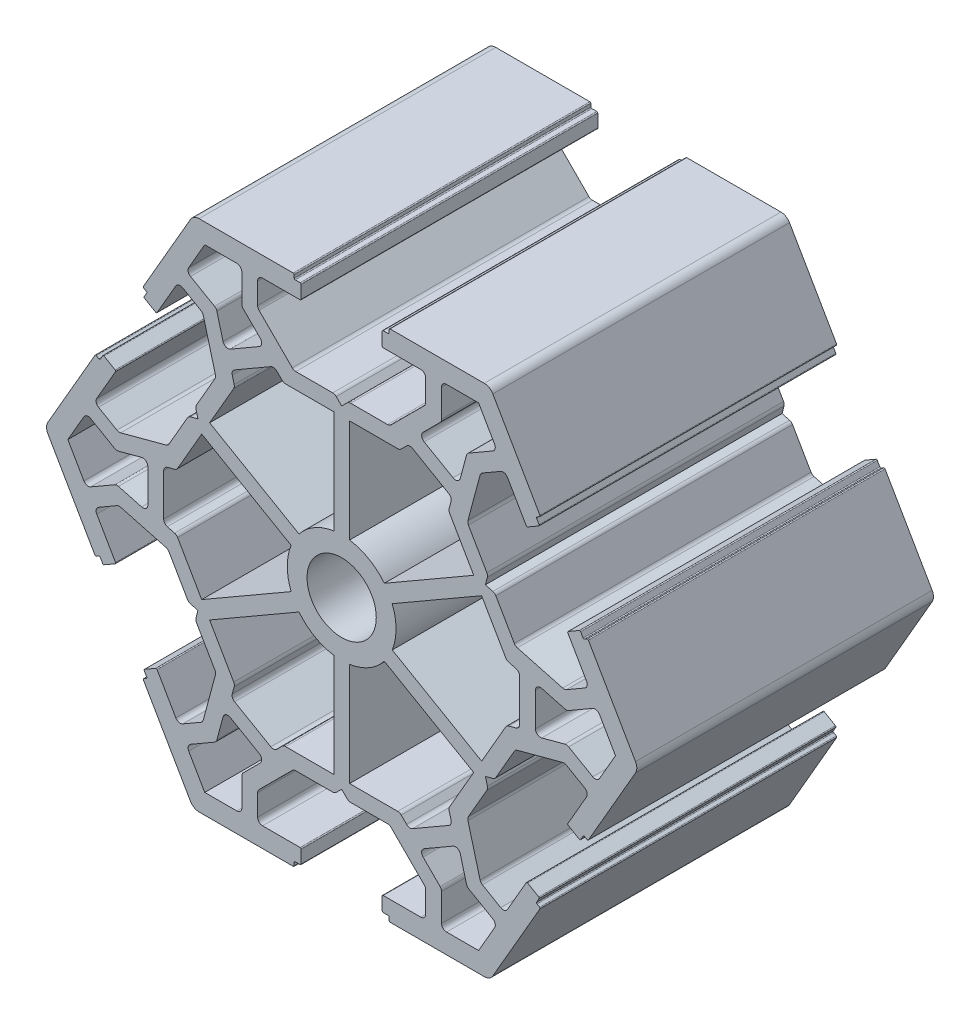
SolidWorks part; units mm, degrees
material "6061 Alaşım"
ref_plane "Ön Düzlem" through (0, 0, 0) normal (0, 0, 1) x (1, 0, 0)
ref_plane "Üst Düzlem" through (0, 0, 0) normal (0, 1, 0) x (1, 0, 0)
ref_plane "Sağ Düzlem" through (0, 0, 0) normal (1, 0, 0) x (0, 0, -1)
sketch "Çizim1" plane through (0, 0, 0) normal (0, 0, 1) x (1, 0, 0)
  line L0 (0, 0) -> (-15, 25.9808) construction
  line L1 (-30, 0) -> (-15, -25.9808) construction
  line L2 (-15, -25.9808) -> (15, -25.9808) construction
  line L3 (15, -25.9808) -> (30, 0) construction
  line L4 (30, 0) -> (15, 25.9808) construction
  line L5 (15, 25.9808) -> (-15, 25.9808) construction
  line L6 (-15, 25.9808) -> (-30, 0) construction
  line L7 (0, 0) -> (-30, 0) construction
  line L8 (0, 0) -> (15, 25.9808) construction
  line L9 (-15.2887, 25.4808) -> (-20.05, 17.2339)
  line L10 (-20.0134, 17.0973) -> (-19.7536, 16.9473)
  line L11 (-19.717, 16.8107) -> (-19.967, 16.3777)
  line L12 (-19.9304, 16.2411) -> (-18.8046, 15.5911)
  line L13 (-18.6679, 15.6277) -> (-16.7679, 18.9186)
  line L14 (-22.5, 12.9904) -> (0, 0) construction
  line L15 (-16.0849, 19.1016) -> (-14.2291, 18.0302)
  line L16 (-13.9962, 17.7265) -> (-12.7674, 13.1407)
  line L17 (-12.8173, 12.7612) -> (-14.6852, 9.526)
  line L18 (-14.7352, 9.1465) -> (-14.5326, 8.3904)
  line L19 (-13.3531, 8.6332) -> (-10.9181, 12.8509)
  line L20 (-10.8681, 13.2303) -> (-11.0658, 13.9679)
  line L21 (-10.8328, 14.5303) -> (-7.1672, 16.6466)
  line L22 (-13.3531, 8.6332) -> (-4.3125, 3.4136)
  line L23 (-13.8453, 23.9808) -> (-15.4679, 21.1703)
  line L24 (-15.2849, 20.4872) -> (-12.8552, 19.0844)
  line L25 (-12.6222, 18.7808) -> (-11.9935, 16.4345)
  line L26 (-11.2606, 16.1308) -> (-8.3394, 17.8173)
  line L27 (-14.5326, 8.3904) -> (-4.7631, 2.75) construction
  line L29 (-9.8, 16.9741) -> (-9, 15.5885)
  line L30 (-9.9536, 20.3216) -> (-8.2359, 18.6039)
  line L31 (-10.1, 23.4808) -> (-10.1, 20.6751)
  line L32 (-13.8453, 23.9808) -> (-10.6, 23.9808)
  line L33 (-14.4226, 25.9808) -> (-4.9, 25.9808)
  line L34 (-4.8, 25.8808) -> (-4.8, 25.5808)
  line L35 (-4.7, 25.4808) -> (-4.2, 25.4808)
  line L36 (-4.1, 25.3808) -> (-4.1, 24.0808)
  line L37 (-4.2, 23.9808) -> (-8, 23.9808)
  line L38 (-8.5, 23.4808) -> (-8.5, 21.3379)
  line L39 (-8.3536, 20.9843) -> (-4.9964, 17.6272)
  line L40 (-4.6429, 17.4808) -> (-0.9071, 17.4808)
  line L41 (-0.5536, 17.3343) -> (0, 16.7808)
  line L42 (0, 16.7808) -> (0, 5.5) construction
  line L43 (-0.8, 15.8808) -> (-0.8, 5.4415)
  line L44 (-0.8, 15.8808) -> (-5.6701, 15.8808)
  line L45 (-6.0237, 16.0272) -> (-6.5636, 16.5672)
  line L46 (15.2887, 25.4808) -> (20.05, 17.2339)
  line L47 (20.0134, 17.0973) -> (19.7536, 16.9473)
  line L48 (19.717, 16.8107) -> (19.967, 16.3777)
  line L49 (19.9304, 16.2411) -> (18.8046, 15.5911)
  line L50 (18.6679, 15.6277) -> (16.7679, 18.9186)
  line L51 (16.0849, 19.1016) -> (14.2291, 18.0302)
  line L52 (13.9962, 17.7265) -> (12.7674, 13.1407)
  line L53 (12.8173, 12.7612) -> (14.6852, 9.526)
  line L54 (14.7352, 9.1465) -> (14.5326, 8.3904)
  line L55 (14.5326, 8.3904) -> (4.7631, 2.75) construction
  line L56 (13.3531, 8.6332) -> (4.3125, 3.4136)
  line L57 (13.3531, 8.6332) -> (10.9181, 12.8509)
  line L58 (10.8681, 13.2303) -> (11.0658, 13.9679)
  line L59 (7.1672, 16.6466) -> (10.8328, 14.5303)
  line L60 (6.0237, 16.0272) -> (6.5636, 16.5672)
  line L61 (0.8, 15.8808) -> (5.6701, 15.8808)
  line L62 (0.8, 15.8808) -> (0.8, 5.4415)
  line L63 (0, 16.7808) -> (0, 5.5) construction
  line L64 (0.5536, 17.3343) -> (0, 16.7808)
  line L65 (4.6429, 17.4808) -> (0.9071, 17.4808)
  line L66 (8.3536, 20.9843) -> (4.9964, 17.6272)
  line L67 (8.5, 23.4808) -> (8.5, 21.3379)
  line L68 (4.2, 23.9808) -> (8, 23.9808)
  line L69 (4.1, 25.3808) -> (4.1, 24.0808)
  line L70 (4.7, 25.4808) -> (4.2, 25.4808)
  line L71 (4.8, 25.8808) -> (4.8, 25.5808)
  line L72 (14.4226, 25.9808) -> (4.9, 25.9808)
  line L73 (13.8453, 23.9808) -> (15.4679, 21.1703)
  line L74 (15.2849, 20.4872) -> (12.8552, 19.0844)
  line L75 (12.6222, 18.7808) -> (11.9935, 16.4345)
  line L76 (8.3394, 17.8173) -> (11.2606, 16.1308)
  line L77 (9.9536, 20.3216) -> (8.2359, 18.6039)
  line L78 (10.1, 23.4808) -> (10.1, 20.6751)
  line L79 (13.8453, 23.9808) -> (10.6, 23.9808)
  line L80 (29.7113, -0.5) -> (24.95, -8.7469)
  line L81 (24.8134, -8.7835) -> (24.5536, -8.6335)
  line L82 (24.417, -8.6701) -> (24.167, -9.1031)
  line L83 (24.0304, -9.1397) -> (22.9046, -8.4897)
  line L84 (22.8679, -8.3531) -> (24.7679, -5.0622)
  line L85 (24.5849, -4.3792) -> (22.7291, -3.3077)
  line L86 (22.3497, -3.2578) -> (17.7638, -4.4866)
  line L87 (17.4602, -4.7195) -> (15.5923, -7.9548)
  line L88 (15.2887, -8.1878) -> (14.5326, -8.3904)
  line L89 (14.5326, -8.3904) -> (4.7631, -2.75) construction
  line L90 (14.1531, -7.2476) -> (5.1125, -2.0279)
  line L91 (14.1531, -7.2476) -> (16.5882, -3.0299)
  line L92 (16.8918, -2.7969) -> (17.6294, -2.5993)
  line L93 (18, 2.1163) -> (18, -2.1163)
  line L94 (16.8918, 2.7969) -> (17.6294, 2.5993)
  line L95 (14.1531, 7.2476) -> (16.5882, 3.0299)
  line L96 (14.1531, 7.2476) -> (5.1125, 2.0279)
  line L97 (14.5326, 8.3904) -> (4.7631, 2.75) construction
  line L98 (15.2887, 8.1878) -> (14.5326, 8.3904)
  line L99 (17.4602, 4.7195) -> (15.5923, 7.9548)
  line L100 (22.3497, 3.2578) -> (17.7638, 4.4866)
  line L101 (24.5849, 4.3792) -> (22.7291, 3.3077)
  line L102 (22.8679, 8.3531) -> (24.7679, 5.0622)
  line L103 (24.0304, 9.1397) -> (22.9046, 8.4897)
  line L104 (24.417, 8.6701) -> (24.167, 9.1031)
  line L105 (24.8134, 8.7835) -> (24.5536, 8.6335)
  line L106 (29.7113, 0.5) -> (24.95, 8.7469)
  line L107 (27.6906, 0) -> (26.0679, -2.8105)
  line L108 (25.3849, -2.9935) -> (22.9552, -1.5907)
  line L109 (22.5758, -1.5408) -> (20.2294, -2.1695)
  line L110 (19.6, 1.6865) -> (19.6, -1.6865)
  line L111 (22.5758, 1.5408) -> (20.2294, 2.1695)
  line L112 (25.3849, 2.9935) -> (22.9552, 1.5907)
  line L113 (27.6906, 0) -> (26.0679, 2.8105)
  line L114 (14.4226, -25.9808) -> (4.9, -25.9808)
  line L115 (4.8, -25.8808) -> (4.8, -25.5808)
  line L116 (4.7, -25.4808) -> (4.2, -25.4808)
  line L117 (4.1, -25.3808) -> (4.1, -24.0808)
  line L118 (4.2, -23.9808) -> (8, -23.9808)
  line L119 (8.5, -23.4808) -> (8.5, -21.3379)
  line L120 (8.3536, -20.9843) -> (4.9964, -17.6272)
  line L121 (4.6429, -17.4808) -> (0.9071, -17.4808)
  line L122 (0.5536, -17.3343) -> (0, -16.7808)
  line L123 (0, -16.7808) -> (0, -5.5) construction
  line L124 (0.8, -15.8808) -> (0.8, -5.4415)
  line L125 (0.8, -15.8808) -> (5.6701, -15.8808)
  line L126 (6.0237, -16.0272) -> (6.5636, -16.5672)
  line L127 (10.8328, -14.5303) -> (7.1672, -16.6466)
  line L128 (10.8681, -13.2303) -> (11.0658, -13.9679)
  line L129 (13.3531, -8.6332) -> (10.9181, -12.8509)
  line L130 (13.3531, -8.6332) -> (4.3125, -3.4136)
  line L131 (14.5326, -8.3904) -> (4.7631, -2.75) construction
  line L132 (14.7352, -9.1465) -> (14.5326, -8.3904)
  line L133 (12.8173, -12.7612) -> (14.6852, -9.526)
  line L134 (13.9962, -17.7265) -> (12.7674, -13.1407)
  line L135 (16.0849, -19.1016) -> (14.2291, -18.0302)
  line L136 (18.6679, -15.6277) -> (16.7679, -18.9186)
  line L137 (19.9304, -16.2411) -> (18.8046, -15.5911)
  line L138 (19.717, -16.8107) -> (19.967, -16.3777)
  line L139 (20.0134, -17.0973) -> (19.7536, -16.9473)
  line L140 (15.2887, -25.4808) -> (20.05, -17.2339)
  line L141 (13.8453, -23.9808) -> (10.6, -23.9808)
  line L142 (10.1, -23.4808) -> (10.1, -20.6751)
  line L143 (9.9536, -20.3216) -> (8.2359, -18.6039)
  line L144 (11.2606, -16.1308) -> (8.3394, -17.8173)
  line L145 (12.6222, -18.7808) -> (11.9935, -16.4345)
  line L146 (15.2849, -20.4872) -> (12.8552, -19.0844)
  line L147 (13.8453, -23.9808) -> (15.4679, -21.1703)
  line L148 (-15.2887, -25.4808) -> (-20.05, -17.2339)
  line L149 (-20.0134, -17.0973) -> (-19.7536, -16.9473)
  line L150 (-19.717, -16.8107) -> (-19.967, -16.3777)
  line L151 (-19.9304, -16.2411) -> (-18.8046, -15.5911)
  line L152 (-18.6679, -15.6277) -> (-16.7679, -18.9186)
  line L153 (-16.0849, -19.1016) -> (-14.2291, -18.0302)
  line L154 (-13.9962, -17.7265) -> (-12.7674, -13.1407)
  line L155 (-12.8173, -12.7612) -> (-14.6852, -9.526)
  line L156 (-14.7352, -9.1465) -> (-14.5326, -8.3904)
  line L157 (-14.5326, -8.3904) -> (-4.7631, -2.75) construction
  line L158 (-13.3531, -8.6332) -> (-4.3125, -3.4136)
  line L159 (-13.3531, -8.6332) -> (-10.9181, -12.8509)
  line L160 (-10.8681, -13.2303) -> (-11.0658, -13.9679)
  line L161 (-7.1672, -16.6466) -> (-10.8328, -14.5303)
  line L162 (-6.0237, -16.0272) -> (-6.5636, -16.5672)
  line L163 (-0.8, -15.8808) -> (-5.6701, -15.8808)
  line L164 (-0.8, -15.8808) -> (-0.8, -5.4415)
  line L165 (0, -16.7808) -> (0, -5.5) construction
  line L166 (-0.5536, -17.3343) -> (0, -16.7808)
  line L167 (-4.6429, -17.4808) -> (-0.9071, -17.4808)
  line L168 (-8.3536, -20.9843) -> (-4.9964, -17.6272)
  line L169 (-8.5, -23.4808) -> (-8.5, -21.3379)
  line L170 (-4.2, -23.9808) -> (-8, -23.9808)
  line L171 (-4.1, -25.3808) -> (-4.1, -24.0808)
  line L172 (-4.7, -25.4808) -> (-4.2, -25.4808)
  line L173 (-4.8, -25.8808) -> (-4.8, -25.5808)
  line L174 (-14.4226, -25.9808) -> (-4.9, -25.9808)
  line L175 (-13.8453, -23.9808) -> (-15.4679, -21.1703)
  line L176 (-15.2849, -20.4872) -> (-12.8552, -19.0844)
  line L177 (-12.6222, -18.7808) -> (-11.9935, -16.4345)
  line L178 (-8.3394, -17.8173) -> (-11.2606, -16.1308)
  line L179 (-9.9536, -20.3216) -> (-8.2359, -18.6039)
  line L180 (-10.1, -23.4808) -> (-10.1, -20.6751)
  line L181 (-13.8453, -23.9808) -> (-10.6, -23.9808)
  line L182 (-29.7113, 0.5) -> (-24.95, 8.7469)
  line L183 (-24.8134, 8.7835) -> (-24.5536, 8.6335)
  line L184 (-24.417, 8.6701) -> (-24.167, 9.1031)
  line L185 (-24.0304, 9.1397) -> (-22.9046, 8.4897)
  line L186 (-22.8679, 8.3531) -> (-24.7679, 5.0622)
  line L187 (-24.5849, 4.3792) -> (-22.7291, 3.3077)
  line L188 (-22.3497, 3.2578) -> (-17.7638, 4.4866)
  line L189 (-17.4602, 4.7195) -> (-15.5923, 7.9548)
  line L190 (-15.2887, 8.1878) -> (-14.5326, 8.3904)
  line L191 (-14.5326, 8.3904) -> (-4.7631, 2.75) construction
  line L192 (-14.1531, 7.2476) -> (-5.1125, 2.0279)
  line L193 (-14.1531, 7.2476) -> (-16.5882, 3.0299)
  line L194 (-16.8918, 2.7969) -> (-17.6294, 2.5993)
  line L195 (-18, -2.1163) -> (-18, 2.1163)
  line L196 (-16.8918, -2.7969) -> (-17.6294, -2.5993)
  line L197 (-14.1531, -7.2476) -> (-16.5882, -3.0299)
  line L198 (-14.1531, -7.2476) -> (-5.1125, -2.0279)
  line L199 (-14.5326, -8.3904) -> (-4.7631, -2.75) construction
  line L200 (-15.2887, -8.1878) -> (-14.5326, -8.3904)
  line L201 (-17.4602, -4.7195) -> (-15.5923, -7.9548)
  line L202 (-22.3497, -3.2578) -> (-17.7638, -4.4866)
  line L203 (-24.5849, -4.3792) -> (-22.7291, -3.3077)
  line L204 (-22.8679, -8.3531) -> (-24.7679, -5.0622)
  line L205 (-24.0304, -9.1397) -> (-22.9046, -8.4897)
  line L206 (-24.417, -8.6701) -> (-24.167, -9.1031)
  line L207 (-24.8134, -8.7835) -> (-24.5536, -8.6335)
  line L208 (-29.7113, -0.5) -> (-24.95, -8.7469)
  line L209 (-27.6906, 0) -> (-26.0679, 2.8105)
  line L210 (-25.3849, 2.9935) -> (-22.9552, 1.5907)
  line L211 (-22.5758, 1.5408) -> (-20.2294, 2.1695)
  line L212 (-19.6, -1.6865) -> (-19.6, 1.6865)
  line L213 (-22.5758, -1.5408) -> (-20.2294, -2.1695)
  line L214 (-25.3849, -2.9935) -> (-22.9552, -1.5907)
  line L215 (-27.6906, 0) -> (-26.0679, -2.8105)
  circle A0 centre (0, 0) radius 25.9808 construction
  circle A1 centre (0, 0) radius 5.5 construction
  arc A2 (-20.05, 17.2339) -> (-20.0134, 17.0973) centre (-19.9634, 17.1839) ccw
  arc A3 (-19.7536, 16.9473) -> (-19.717, 16.8107) centre (-19.8036, 16.8607) cw
  arc A4 (-19.967, 16.3777) -> (-19.9304, 16.2411) centre (-19.8804, 16.3277) ccw
  arc A5 (-18.8046, 15.5911) -> (-18.6679, 15.6277) centre (-18.7546, 15.6777) ccw
  arc A6 (-15.4679, 21.1703) -> (-15.2849, 20.4872) centre (-15.0349, 20.9203) ccw
  arc A7 (-16.7679, 18.9186) -> (-16.0849, 19.1016) centre (-16.3349, 18.6686) cw
  arc A8 (-14.2291, 18.0302) -> (-13.9962, 17.7265) centre (-14.4791, 17.5971) cw
  arc A9 (-12.8552, 19.0844) -> (-12.6222, 18.7808) centre (-13.1052, 18.6514) cw
  arc A10 (-11.9935, 16.4345) -> (-11.2606, 16.1308) centre (-11.5106, 16.5639) ccw
  arc A11 (-11.0658, 13.9679) -> (-10.8328, 14.5303) centre (-10.5828, 14.0973) cw
  arc A12 (-14.6852, 9.526) -> (-14.7352, 9.1465) centre (-14.2522, 9.276) ccw
  arc A13 (-12.7674, 13.1407) -> (-12.8173, 12.7612) centre (-13.2504, 13.0112) cw
  arc A14 (-10.9181, 12.8509) -> (-10.8681, 13.2303) centre (-11.3511, 13.1009) ccw
  arc A15 (-4.7631, 2.75) -> (-4.3125, 3.4136) centre (0, 0) cw
  arc A16 (-8.2359, 18.6039) -> (-8.3394, 17.8173) centre (-8.5894, 18.2504) cw
  arc A17 (-10.1, 20.6751) -> (-9.9536, 20.3216) centre (-9.6, 20.6751) ccw
  arc A18 (-10.6, 23.9808) -> (-10.1, 23.4808) centre (-10.6, 23.4808) cw
  arc A19 (-4.9, 25.9808) -> (-4.8, 25.8808) centre (-4.9, 25.8808) cw
  arc A20 (-4.8, 25.5808) -> (-4.7, 25.4808) centre (-4.7, 25.5808) ccw
  arc A21 (-4.2, 25.4808) -> (-4.1, 25.3808) centre (-4.2, 25.3808) cw
  arc A22 (-4.1, 24.0808) -> (-4.2, 23.9808) centre (-4.2, 24.0808) cw
  arc A23 (-8, 23.9808) -> (-8.5, 23.4808) centre (-8, 23.4808) ccw
  arc A24 (-8.5, 21.3379) -> (-8.3536, 20.9843) centre (-8, 21.3379) ccw
  arc A25 (-4.9964, 17.6272) -> (-4.6429, 17.4808) centre (-4.6429, 17.9808) ccw
  arc A26 (-0.9071, 17.4808) -> (-0.5536, 17.3343) centre (-0.9071, 16.9808) cw
  arc A27 (0, 5.5) -> (-0.8, 5.4415) centre (0, 0) ccw
  arc A28 (-5.6701, 15.8808) -> (-6.0237, 16.0272) centre (-5.6701, 16.3808) cw
  arc A29 (-6.5636, 16.5672) -> (-7.1672, 16.6466) centre (-6.9172, 16.2136) ccw
  arc A30 (-14.4226, 25.9808) -> (-15.2887, 25.4808) centre (-14.4226, 24.9808) ccw
  arc A31 (15.2887, 25.4808) -> (14.4226, 25.9808) centre (14.4226, 24.9808) ccw
  arc A32 (20.05, 17.2339) -> (20.0134, 17.0973) centre (19.9634, 17.1839) cw
  arc A33 (19.7536, 16.9473) -> (19.717, 16.8107) centre (19.8036, 16.8607) ccw
  arc A34 (19.967, 16.3777) -> (19.9304, 16.2411) centre (19.8804, 16.3277) cw
  arc A35 (18.8046, 15.5911) -> (18.6679, 15.6277) centre (18.7546, 15.6777) cw
  arc A36 (16.7679, 18.9186) -> (16.0849, 19.1016) centre (16.3349, 18.6686) ccw
  arc A37 (14.2291, 18.0302) -> (13.9962, 17.7265) centre (14.4791, 17.5971) ccw
  arc A38 (12.7674, 13.1407) -> (12.8173, 12.7612) centre (13.2504, 13.0112) ccw
  arc A39 (14.6852, 9.526) -> (14.7352, 9.1465) centre (14.2522, 9.276) cw
  arc A40 (4.7631, 2.75) -> (4.3125, 3.4136) centre (0, 0) ccw
  arc A41 (10.9181, 12.8509) -> (10.8681, 13.2303) centre (11.3511, 13.1009) cw
  arc A42 (11.0658, 13.9679) -> (10.8328, 14.5303) centre (10.5828, 14.0973) ccw
  arc A43 (6.5636, 16.5672) -> (7.1672, 16.6466) centre (6.9172, 16.2136) cw
  arc A44 (5.6701, 15.8808) -> (6.0237, 16.0272) centre (5.6701, 16.3808) ccw
  arc A45 (0, 5.5) -> (0.8, 5.4415) centre (0, 0) cw
  arc A46 (0.9071, 17.4808) -> (0.5536, 17.3343) centre (0.9071, 16.9808) ccw
  arc A47 (4.9964, 17.6272) -> (4.6429, 17.4808) centre (4.6429, 17.9808) cw
  arc A48 (8.5, 21.3379) -> (8.3536, 20.9843) centre (8, 21.3379) cw
  arc A49 (8, 23.9808) -> (8.5, 23.4808) centre (8, 23.4808) cw
  arc A50 (4.1, 24.0808) -> (4.2, 23.9808) centre (4.2, 24.0808) ccw
  arc A51 (4.2, 25.4808) -> (4.1, 25.3808) centre (4.2, 25.3808) ccw
  arc A52 (4.8, 25.5808) -> (4.7, 25.4808) centre (4.7, 25.5808) cw
  arc A53 (4.9, 25.9808) -> (4.8, 25.8808) centre (4.9, 25.8808) ccw
  arc A54 (15.4679, 21.1703) -> (15.2849, 20.4872) centre (15.0349, 20.9203) cw
  arc A55 (12.8552, 19.0844) -> (12.6222, 18.7808) centre (13.1052, 18.6514) ccw
  arc A56 (11.9935, 16.4345) -> (11.2606, 16.1308) centre (11.5106, 16.5639) cw
  arc A57 (8.2359, 18.6039) -> (8.3394, 17.8173) centre (8.5894, 18.2504) ccw
  arc A58 (10.1, 20.6751) -> (9.9536, 20.3216) centre (9.6, 20.6751) cw
  arc A59 (10.6, 23.9808) -> (10.1, 23.4808) centre (10.6, 23.4808) ccw
  arc A60 (29.7113, -0.5) -> (29.7113, 0.5) centre (28.8453, 0) ccw
  arc A61 (24.95, -8.7469) -> (24.8134, -8.7835) centre (24.8634, -8.6969) cw
  arc A62 (24.5536, -8.6335) -> (24.417, -8.6701) centre (24.5036, -8.7201) ccw
  arc A63 (24.167, -9.1031) -> (24.0304, -9.1397) centre (24.0804, -9.0531) cw
  arc A64 (22.9046, -8.4897) -> (22.8679, -8.3531) centre (22.9546, -8.4031) cw
  arc A65 (24.7679, -5.0622) -> (24.5849, -4.3792) centre (24.3349, -4.8122) ccw
  arc A66 (22.7291, -3.3077) -> (22.3497, -3.2578) centre (22.4791, -3.7407) ccw
  arc A67 (17.7638, -4.4866) -> (17.4602, -4.7195) centre (17.8932, -4.9695) ccw
  arc A68 (15.5923, -7.9548) -> (15.2887, -8.1878) centre (15.1593, -7.7048) cw
  arc A69 (4.7631, -2.75) -> (5.1125, -2.0279) centre (0, 0) ccw
  arc A70 (16.5882, -3.0299) -> (16.8918, -2.7969) centre (17.0212, -3.2799) cw
  arc A71 (17.6294, -2.5993) -> (18, -2.1163) centre (17.5, -2.1163) ccw
  arc A72 (17.6294, 2.5993) -> (18, 2.1163) centre (17.5, 2.1163) cw
  arc A73 (16.5882, 3.0299) -> (16.8918, 2.7969) centre (17.0212, 3.2799) ccw
  arc A74 (4.7631, 2.75) -> (5.1125, 2.0279) centre (0, 0) cw
  arc A75 (15.5923, 7.9548) -> (15.2887, 8.1878) centre (15.1593, 7.7048) ccw
  arc A76 (17.7638, 4.4866) -> (17.4602, 4.7195) centre (17.8932, 4.9695) cw
  arc A77 (22.7291, 3.3077) -> (22.3497, 3.2578) centre (22.4791, 3.7407) cw
  arc A78 (24.7679, 5.0622) -> (24.5849, 4.3792) centre (24.3349, 4.8122) cw
  arc A79 (22.9046, 8.4897) -> (22.8679, 8.3531) centre (22.9546, 8.4031) ccw
  arc A80 (24.167, 9.1031) -> (24.0304, 9.1397) centre (24.0804, 9.0531) ccw
  arc A81 (24.5536, 8.6335) -> (24.417, 8.6701) centre (24.5036, 8.7201) cw
  arc A82 (24.95, 8.7469) -> (24.8134, 8.7835) centre (24.8634, 8.6969) ccw
  arc A83 (26.0679, -2.8105) -> (25.3849, -2.9935) centre (25.6349, -2.5605) cw
  arc A84 (22.9552, -1.5907) -> (22.5758, -1.5408) centre (22.7052, -2.0237) ccw
  arc A85 (20.2294, -2.1695) -> (19.6, -1.6865) centre (20.1, -1.6865) cw
  arc A86 (20.2294, 2.1695) -> (19.6, 1.6865) centre (20.1, 1.6865) ccw
  arc A87 (22.9552, 1.5907) -> (22.5758, 1.5408) centre (22.7052, 2.0237) cw
  arc A88 (26.0679, 2.8105) -> (25.3849, 2.9935) centre (25.6349, 2.5605) ccw
  arc A89 (14.4226, -25.9808) -> (15.2887, -25.4808) centre (14.4226, -24.9808) ccw
  arc A90 (4.9, -25.9808) -> (4.8, -25.8808) centre (4.9, -25.8808) cw
  arc A91 (4.8, -25.5808) -> (4.7, -25.4808) centre (4.7, -25.5808) ccw
  arc A92 (4.2, -25.4808) -> (4.1, -25.3808) centre (4.2, -25.3808) cw
  arc A93 (4.1, -24.0808) -> (4.2, -23.9808) centre (4.2, -24.0808) cw
  arc A94 (8, -23.9808) -> (8.5, -23.4808) centre (8, -23.4808) ccw
  arc A95 (8.5, -21.3379) -> (8.3536, -20.9843) centre (8, -21.3379) ccw
  arc A96 (4.9964, -17.6272) -> (4.6429, -17.4808) centre (4.6429, -17.9808) ccw
  arc A97 (0.9071, -17.4808) -> (0.5536, -17.3343) centre (0.9071, -16.9808) cw
  arc A99 (5.6701, -15.8808) -> (6.0237, -16.0272) centre (5.6701, -16.3808) cw
  arc A100 (6.5636, -16.5672) -> (7.1672, -16.6466) centre (6.9172, -16.2136) ccw
  arc A101 (11.0658, -13.9679) -> (10.8328, -14.5303) centre (10.5828, -14.0973) cw
  arc A102 (10.9181, -12.8509) -> (10.8681, -13.2303) centre (11.3511, -13.1009) ccw
  arc A103 (4.7631, -2.75) -> (4.3125, -3.4136) centre (0, 0) cw
  arc A104 (14.6852, -9.526) -> (14.7352, -9.1465) centre (14.2522, -9.276) ccw
  arc A105 (12.7674, -13.1407) -> (12.8173, -12.7612) centre (13.2504, -13.0112) cw
  arc A106 (14.2291, -18.0302) -> (13.9962, -17.7265) centre (14.4791, -17.5971) cw
  arc A107 (16.7679, -18.9186) -> (16.0849, -19.1016) centre (16.3349, -18.6686) cw
  arc A108 (18.8046, -15.5911) -> (18.6679, -15.6277) centre (18.7546, -15.6777) ccw
  arc A109 (19.967, -16.3777) -> (19.9304, -16.2411) centre (19.8804, -16.3277) ccw
  arc A110 (19.7536, -16.9473) -> (19.717, -16.8107) centre (19.8036, -16.8607) cw
  arc A111 (20.05, -17.2339) -> (20.0134, -17.0973) centre (19.9634, -17.1839) ccw
  arc A112 (10.6, -23.9808) -> (10.1, -23.4808) centre (10.6, -23.4808) cw
  arc A113 (10.1, -20.6751) -> (9.9536, -20.3216) centre (9.6, -20.6751) ccw
  arc A114 (8.2359, -18.6039) -> (8.3394, -17.8173) centre (8.5894, -18.2504) cw
  arc A115 (11.9935, -16.4345) -> (11.2606, -16.1308) centre (11.5106, -16.5639) ccw
  arc A116 (12.8552, -19.0844) -> (12.6222, -18.7808) centre (13.1052, -18.6514) cw
  arc A117 (15.4679, -21.1703) -> (15.2849, -20.4872) centre (15.0349, -20.9203) ccw
  arc A118 (-15.2887, -25.4808) -> (-14.4226, -25.9808) centre (-14.4226, -24.9808) ccw
  arc A119 (-20.05, -17.2339) -> (-20.0134, -17.0973) centre (-19.9634, -17.1839) cw
  arc A120 (-19.7536, -16.9473) -> (-19.717, -16.8107) centre (-19.8036, -16.8607) ccw
  arc A121 (-19.967, -16.3777) -> (-19.9304, -16.2411) centre (-19.8804, -16.3277) cw
  arc A122 (-18.8046, -15.5911) -> (-18.6679, -15.6277) centre (-18.7546, -15.6777) cw
  arc A123 (-16.7679, -18.9186) -> (-16.0849, -19.1016) centre (-16.3349, -18.6686) ccw
  arc A124 (-14.2291, -18.0302) -> (-13.9962, -17.7265) centre (-14.4791, -17.5971) ccw
  arc A125 (-12.7674, -13.1407) -> (-12.8173, -12.7612) centre (-13.2504, -13.0112) ccw
  arc A126 (-14.6852, -9.526) -> (-14.7352, -9.1465) centre (-14.2522, -9.276) cw
  arc A127 (-4.7631, -2.75) -> (-4.3125, -3.4136) centre (0, 0) ccw
  arc A128 (-10.9181, -12.8509) -> (-10.8681, -13.2303) centre (-11.3511, -13.1009) cw
  arc A129 (-11.0658, -13.9679) -> (-10.8328, -14.5303) centre (-10.5828, -14.0973) ccw
  arc A130 (-6.5636, -16.5672) -> (-7.1672, -16.6466) centre (-6.9172, -16.2136) cw
  arc A131 (-5.6701, -15.8808) -> (-6.0237, -16.0272) centre (-5.6701, -16.3808) ccw
  arc A133 (-0.9071, -17.4808) -> (-0.5536, -17.3343) centre (-0.9071, -16.9808) ccw
  arc A134 (-4.9964, -17.6272) -> (-4.6429, -17.4808) centre (-4.6429, -17.9808) cw
  arc A135 (-8.5, -21.3379) -> (-8.3536, -20.9843) centre (-8, -21.3379) cw
  arc A136 (-8, -23.9808) -> (-8.5, -23.4808) centre (-8, -23.4808) cw
  arc A137 (-4.1, -24.0808) -> (-4.2, -23.9808) centre (-4.2, -24.0808) ccw
  arc A138 (-4.2, -25.4808) -> (-4.1, -25.3808) centre (-4.2, -25.3808) ccw
  arc A139 (-4.8, -25.5808) -> (-4.7, -25.4808) centre (-4.7, -25.5808) cw
  arc A140 (-4.9, -25.9808) -> (-4.8, -25.8808) centre (-4.9, -25.8808) ccw
  arc A141 (-15.4679, -21.1703) -> (-15.2849, -20.4872) centre (-15.0349, -20.9203) cw
  arc A142 (-12.8552, -19.0844) -> (-12.6222, -18.7808) centre (-13.1052, -18.6514) ccw
  arc A143 (-11.9935, -16.4345) -> (-11.2606, -16.1308) centre (-11.5106, -16.5639) cw
  arc A144 (-8.2359, -18.6039) -> (-8.3394, -17.8173) centre (-8.5894, -18.2504) ccw
  arc A145 (-10.1, -20.6751) -> (-9.9536, -20.3216) centre (-9.6, -20.6751) cw
  arc A146 (-10.6, -23.9808) -> (-10.1, -23.4808) centre (-10.6, -23.4808) ccw
  arc A147 (-29.7113, 0.5) -> (-29.7113, -0.5) centre (-28.8453, 0) ccw
  arc A148 (-24.95, 8.7469) -> (-24.8134, 8.7835) centre (-24.8634, 8.6969) cw
  arc A149 (-24.5536, 8.6335) -> (-24.417, 8.6701) centre (-24.5036, 8.7201) ccw
  arc A150 (-24.167, 9.1031) -> (-24.0304, 9.1397) centre (-24.0804, 9.0531) cw
  arc A151 (-22.9046, 8.4897) -> (-22.8679, 8.3531) centre (-22.9546, 8.4031) cw
  arc A152 (-24.7679, 5.0622) -> (-24.5849, 4.3792) centre (-24.3349, 4.8122) ccw
  arc A153 (-22.7291, 3.3077) -> (-22.3497, 3.2578) centre (-22.4791, 3.7407) ccw
  arc A154 (-17.7638, 4.4866) -> (-17.4602, 4.7195) centre (-17.8932, 4.9695) ccw
  arc A155 (-15.5923, 7.9548) -> (-15.2887, 8.1878) centre (-15.1593, 7.7048) cw
  arc A156 (-4.7631, 2.75) -> (-5.1125, 2.0279) centre (0, 0) ccw
  arc A157 (-16.5882, 3.0299) -> (-16.8918, 2.7969) centre (-17.0212, 3.2799) cw
  arc A158 (-17.6294, 2.5993) -> (-18, 2.1163) centre (-17.5, 2.1163) ccw
  arc A159 (-17.6294, -2.5993) -> (-18, -2.1163) centre (-17.5, -2.1163) cw
  arc A160 (-16.5882, -3.0299) -> (-16.8918, -2.7969) centre (-17.0212, -3.2799) ccw
  arc A162 (-15.5923, -7.9548) -> (-15.2887, -8.1878) centre (-15.1593, -7.7048) ccw
  arc A163 (-17.7638, -4.4866) -> (-17.4602, -4.7195) centre (-17.8932, -4.9695) cw
  arc A164 (-22.7291, -3.3077) -> (-22.3497, -3.2578) centre (-22.4791, -3.7407) cw
  arc A165 (-24.7679, -5.0622) -> (-24.5849, -4.3792) centre (-24.3349, -4.8122) cw
  arc A166 (-22.9046, -8.4897) -> (-22.8679, -8.3531) centre (-22.9546, -8.4031) ccw
  arc A167 (-24.167, -9.1031) -> (-24.0304, -9.1397) centre (-24.0804, -9.0531) ccw
  arc A168 (-24.5536, -8.6335) -> (-24.417, -8.6701) centre (-24.5036, -8.7201) cw
  arc A169 (-24.95, -8.7469) -> (-24.8134, -8.7835) centre (-24.8634, -8.6969) ccw
  arc A170 (-26.0679, 2.8105) -> (-25.3849, 2.9935) centre (-25.6349, 2.5605) cw
  arc A171 (-22.9552, 1.5907) -> (-22.5758, 1.5408) centre (-22.7052, 2.0237) ccw
  arc A172 (-20.2294, 2.1695) -> (-19.6, 1.6865) centre (-20.1, 1.6865) cw
  arc A173 (-20.2294, -2.1695) -> (-19.6, -1.6865) centre (-20.1, -1.6865) ccw
  arc A174 (-22.9552, -1.5907) -> (-22.5758, -1.5408) centre (-22.7052, -2.0237) cw
  arc A175 (-26.0679, -2.8105) -> (-25.3849, -2.9935) centre (-25.6349, -2.5605) ccw
  circle A176 centre (0, 0) radius 3.5
  arc A177 (-5.1125, -2.0279) -> (-5.1125, 2.0279) centre (0, 0) cw
  arc A178 (-4.3125, 3.4136) -> (-0.8, 5.4415) centre (0, 0) cw
  arc A179 (0, -5.5) -> (-0.8, -5.4415) centre (0, 0) cw [skipped]
  arc A180 (0, -5.5) -> (0.8, -5.4415) centre (0, 0) ccw [skipped]
  arc A181 (-4.7631, -2.75) -> (-5.1125, -2.0279) centre (0, 0) cw [skipped]
  circle A182 centre (0, 0) radius 5.5
  point P32 (-20.1, 17.1473)
  point P35 (-19.667, 16.8973)
  point P38 (-20.017, 16.2911)
  point P45 (-16.5179, 19.3516)
  point P48 (-14.0498, 17.9266)
  point P55 (-11.1651, 14.3385)
  point P562 (0, 0)
  dimension "D12" = 11
  dimension "D15" = 0.1
  dimension "D22" = 0.5
  dimension "D24" = 1
  dimension "D26" = 7
  dimension "D1" = 60
  dimension "D2" = 2
  dimension "D3" = 0.5
  dimension "D4" = 0.7
  dimension "D5" = 8.2
  dimension "D6" = 8.5
  dimension "D7" = 135
  dimension "D8" = 6.5
  dimension "D9" = 135
  dimension "D10" = 9.2
  dimension "D11" = 2.85
  dimension "D13" = 1.6
  dimension "D14" = 1.6
  dimension "D16" = 2.5
  dimension "D17" = 12
  dimension "D18" = 1.6
  dimension "D19" = 1.6
  dimension "D20" = 1.6
  dimension "D21" = 2
  dimension "D23" = 30
  dimension "D25" = 6
extrude "Yükseklik-Ekstrüzyon1" add sketch "Çizim1" along normal blind 30 contours L208 A169 L207 A168 L206 A167 L205 A166 L204 A165 L203 A164 L202 A163 L201 A162 L200 L156 A126 L155 A125 L154 A124 L153 A123 L152 A122 L151 A121 L150 A120 L149 A119 L148 A118 L174 A140 L173 A139 L172 A138 L171 A137 L170 A136 L169 A135 L168 A134 L167 A133 | A40 A182 A45 A27 A178 A15 A156 A177 A127 A103 A69 A74 A176 region at (-14.527, 25.1614, 0) region at (-2.6722, 4.6284, 0)
